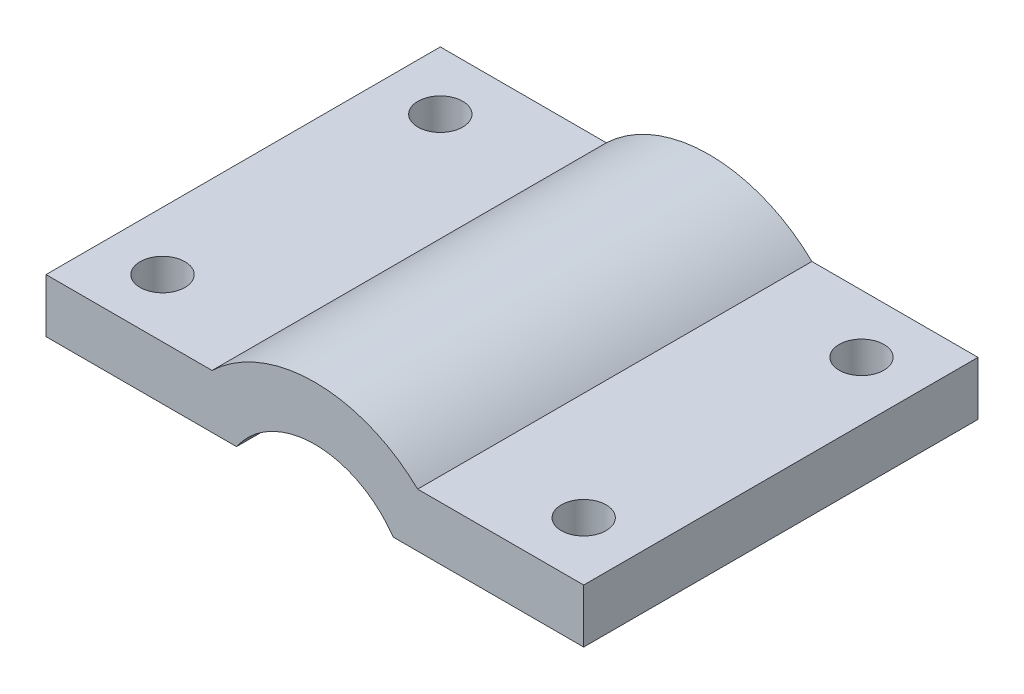
SolidWorks part; units mm, degrees
material "Custom Plastic"
ref_plane "Front Plane" through (0, 0, 0) normal (0, 0, 1) x (1, 0, 0)
ref_plane "Top Plane" through (0, 0, 0) normal (0, 1, 0) x (1, 0, 0)
ref_plane "Right Plane" through (0, 0, 0) normal (1, 0, 0) x (0, 0, -1)
sketch "Sketch3" plane through (0, 0, 0) normal (0, 0, 1) x (1, 0, 0)
  line L0 (-15, 3) -> (-4.3692, 3)
  line L1 (15, 3) -> (15, 6)
  line L2 (15, 6) -> (5.735, 6)
  line L3 (-15, 6) -> (15, 6) construction
  line L4 (-15, 6) -> (-15, 3)
  line L5 (4.3692, 3) -> (15, 3)
  line L6 (-5.735, 6) -> (-15, 6)
  line L7 (-15, -19) -> (15, -19) construction
  arc A0 (4.3692, 3) -> (-4.3692, 3) centre (0, 0) ccw
  arc A1 (5.735, 6) -> (-5.735, 6) centre (0, 0) ccw
  circle A2 centre (0, 0) radius 5.3 construction
  dimension "D1" = 3
  dimension "D3" = 3
  dimension "D6" = 3
extrude "Boss-Extrude1" add sketch "Sketch3" along normal blind 22
sketch "Sketch4" plane through (0, 6, 0) normal (0, 1, 0) x (1, 0, 0)
  line L1 (15, 0) -> (5.735, 0) construction
  line L2 (-5.735, 0) -> (-15, 0) construction
  line L3 (-5.735, -22) -> (-15, -22) construction
  line L4 (-15, -22) -> (-15, 0) construction
  line L5 (15, -22) -> (15, 0) construction
  line L6 (15, -22) -> (5.735, -22) construction
  circle A4 centre (11.75, -18.75) radius 1.25
  circle A5 centre (11.75, -3.25) radius 1.25
  circle A6 centre (-11.75, -3.25) radius 1.25
  circle A7 centre (-11.75, -18.75) radius 1.25
  circle A8 centre (11.75, -18.75) radius 3.25 construction
  circle A9 centre (11.75, -3.25) radius 3.25 construction
  circle A10 centre (-11.75, -3.25) radius 3.25 construction
  circle A11 centre (-11.75, -18.75) radius 3.25 construction
  dimension "D2" = 2.5
  dimension "D1" = 2
extrude "Cut-Extrude1" cut sketch "Sketch4" against normal up to surface (3 mm away) up to face at (9.6846, 3, 11)
